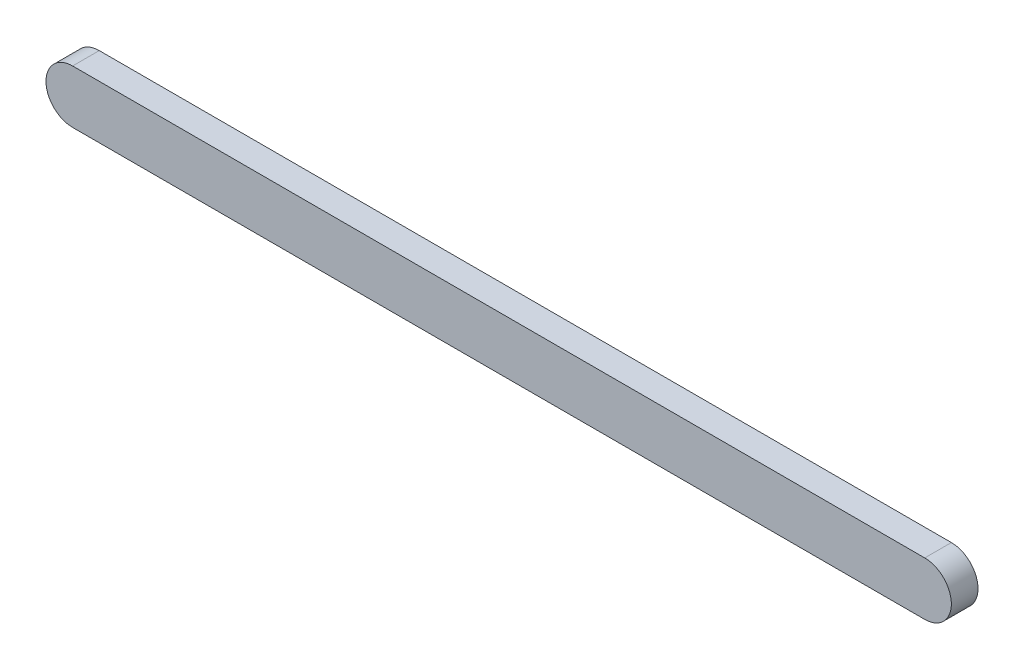
SolidWorks part; units mm, degrees
ref_plane "Front Plane" through (0, 0, 0) normal (0, 0, 1) x (1, 0, 0)
ref_plane "Top Plane" through (0, 0, 0) normal (0, 1, 0) x (1, 0, 0)
ref_plane "Right Plane" through (0, 0, 0) normal (1, 0, 0) x (0, 0, -1)
sketch "Sketch3" plane through (0, 0, 0) normal (0, 0, 1) x (1, 0, 0)
  line L0 (0, 0) -> (80, 0) construction
  line L1 (0, 2.5) -> (80, 2.5)
  line L2 (0, -2.5) -> (80, -2.5)
  arc A0 (0, 2.5) -> (0, -2.5) centre (0, 0) ccw
  arc A1 (80, -2.5) -> (80, 2.5) centre (80, 0) ccw
  point P3 (40, 0)
extrude "Boss-Extrude1" add sketch "Sketch3" along normal blind 2.5
ref_axis "Axis2" through (0, 0, 2.5) along (0, 0, -1)
ref_axis "Axis3" through (80, 0, 2.5) along (0, 0, -1)
